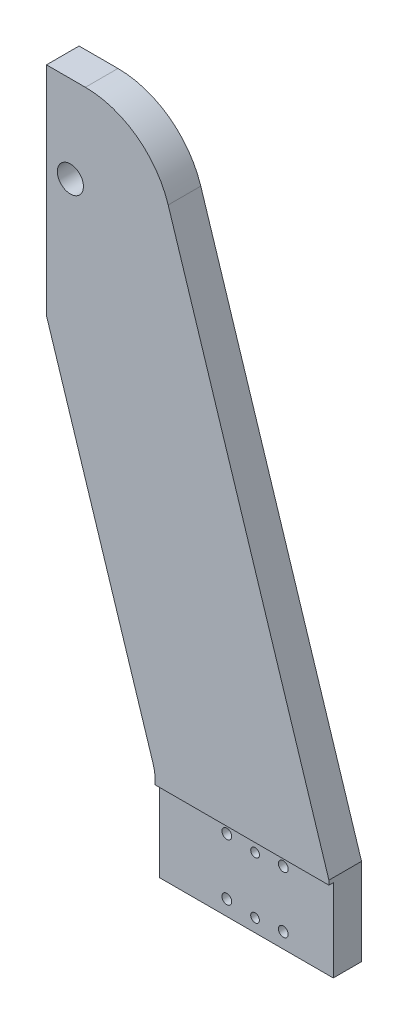
SolidWorks part; units mm, degrees
ref_plane "Alzado" through (0, 0, 0) normal (0, 0, 1) x (1, 0, 0)
ref_plane "Planta" through (0, 0, 0) normal (0, 1, 0) x (1, 0, 0)
ref_plane "Vista lateral" through (0, 0, 0) normal (1, 0, 0) x (0, 0, -1)
sketch "Croquis1" plane through (0, 0, 0) normal (0, 0, 1) x (1, 0, 0)
  line L0 (80, 0) -> (80, 40)
  line L1 (-50, 300) -> (-32.095, 300)
  line L2 (-50, 300) -> (-50, 200)
  line L3 (0, 0) -> (80, 0)
  line L4 (6.0164, 272.1459) -> (80, 40)
  line L9 (-50, 200) -> (-0.9443, 46.0729)
  line L11 (0, 40) -> (0, 0)
  arc A2 (6.0164, 272.1459) -> (-32.095, 300) centre (-32.095, 260) ccw
  arc A3 (-0.9443, 46.0729) -> (0, 40) centre (-20, 40) cw
  dimension "D7" = 40
  dimension "D9" = 40
  dimension "D4" = 20
  dimension "D1" = 50
  dimension "D2" = 300
  dimension "D3" = 80
  dimension "D5" = 100
  dimension "D6" = 40
extrude "Saliente-Extruir1" add sketch "Croquis1" along normal blind 15
sketch "Croquis2" plane through (0, 0, 0) normal (0, 0, -1) x (-1, 0, 0)
  line L0 (32.095, 300) -> (50, 300) construction
  line L2 (50, 300) -> (50, 200) construction
  circle A0 centre (39, 260) radius 6
  dimension "D3" = 12
  dimension "D1" = 40
  dimension "D2" = 11
extrude "Cortar-Extruir1" cut sketch "Croquis2" against normal through all
hole_wizard "Perforador para roscar para macho de roscar para M44" positions "Croquis7" profile "Croquis8" hole size "M4" standard "DIN"
sketch "Croquis7" plane through (0, 0, 0) normal (0, 0, -1) x (-1, 0, 0)
  line L0 (39, 278.25) -> (39, 241.75)
  circle A0 centre (39, 260) radius 6 construction
  point P10 (39, 278.25)
  point P12 (39, 241.75)
  dimension "D1" = 18.25
  dimension "D2" = 18.25
sketch "Croquis8" plane through (-39, 241.75, 0) normal (1, 0, 0) x (0, 1, 0)
  line L0 (0, 0) -> (0, 7.9914)
  line L1 (0, 7.9914) -> (1.65, 7)
  line L2 (1.65, 7) -> (1.65, 0)
  line L5 (1.65, 0) -> (0, 0)
  line L10 (0, 7.9914) -> (-1.65, 7) construction
  line L11 (0, -6.35) -> (0, 107.95) construction
  dimension "Diámetro de taladro" = 3.3
  dimension "Profundidad de taladro" = 7
  dimension "Ángulo de perforador" = 118
sketch "Croquis9" plane through (0, 0, 15) normal (0, 0, 1) x (1, 0, 0)
  line L1 (0, 0) -> (80, 0)
  line L2 (0, 0) -> (0, 38)
  line L3 (0, 38) -> (80, 38)
  line L4 (80, 0) -> (80, 38)
  dimension "D1" = 80
  dimension "D2" = 38
extrude "Cortar-Extruir2" cut sketch "Croquis9" against normal blind 2
hole_wizard "Taladros de espiga de Ø4.0mm1" positions "Croquis10" profile "Croquis12" hole size "Ø4.0" standard "DIN"
sketch "Croquis10" plane through (-50, 0, 0) normal (-1, 0, 0) x (0, 0, 1)
  line L0 (0, 300) -> (0, 200) construction
  line L1 (15, 300) -> (0, 300) construction
  point P0 (6, 274)
  point P2 (6, 246)
  dimension "D1" = 6
  dimension "D2" = 6
  dimension "D3" = 26
  dimension "D4" = 54
sketch "Croquis12" plane through (-50, 274, 6) normal (0, 1, 0) x (0, 0, 1)
  line L0 (0, 0) -> (0, 18.2017)
  line L1 (0, 18.2017) -> (2, 17)
  line L2 (2, 17) -> (2, 0)
  line L5 (2, 0) -> (0, 0)
  line L10 (0, 18.2017) -> (-2, 17) construction
  line L11 (0, -6.35) -> (0, 107.95) construction
  dimension "Diámetro de taladro" = 4
  dimension "Profundidad de taladro" = 17
  dimension "Ángulo de perforador" = 118
hole_wizard "Taladro roscado M41" positions "Croquis13" profile "Croquis14" tap size "M4" standard "DIN"
sketch "Croquis13" plane through (-50, 0, 0) normal (-1, 0, 0) x (0, 0, 1)
  line L0 (0, 300) -> (0, 200) construction
  line L1 (15, 300) -> (0, 300) construction
  point P0 (6, 285)
  point P2 (6, 235)
  dimension "D1" = 6
  dimension "D2" = 6
  dimension "D3" = 15
  dimension "D4" = 65
sketch "Croquis14" plane through (-50, 285, 6) normal (0, 1, 0) x (0, 0, 1)
  line L0 (0, 0) -> (0, 12.4914)
  line L1 (0, 12.4914) -> (1.65, 11.5)
  line L2 (1.65, 11.5) -> (1.65, 0)
  line L5 (1.65, 0) -> (0, 0)
  line L10 (0, 12.4914) -> (-1.65, 11.5) construction
  line L11 (0, -6.35) -> (0, 107.95) construction
  dimension "Diámetro de perforador para roscar" = 3.3
  dimension "Profundidad de perforador para roscar" = 11.5
  dimension "Ángulo de perforador" = 118
cosmetic thread "Rosca de taladro1" parameters "D1"=8, "D2"=4
cosmetic thread "Rosca de taladro2" parameters "D1"=8, "D2"=4
hole_wizard "Refrentado para tornillo con cabeza hueca de M41" positions "Croquis15" profile "Croquis16" counterbore size "M4" standard "DIN" end condition through all
sketch "Croquis15" plane through (0, 0, 0) normal (0, 0, -1) x (-1, 0, 0)
  line L1 (-57, 7) -> (-31, 7)
  line L2 (-57, 7) -> (-57, 33)
  line L3 (-57, 33) -> (-31, 33)
  line L4 (-31, 7) -> (-31, 33)
  line L5 (-57, 7) -> (-31, 33) construction
  line L6 (-57, 33) -> (-31, 7) construction
  line L16 (0, 0) -> (-80, 0) construction
  line L17 (-80, 0) -> (-80, 40) construction
  point P148 (-57, 33)
  point P151 (-31, 33)
  point P154 (-31, 7)
  point P157 (-57, 7)
  dimension "D1" = 26
  dimension "D2" = 26
  dimension "D3" = 23
  dimension "D4" = 7
sketch "Croquis16" plane through (57, 7, 0) normal (1, 0, 0) x (0, 1, 0)
  line L0 (0, 0) -> (0, 15)
  line L1 (0, 15) -> (2.25, 15)
  line L3 (2.25, 15) -> (2.25, 4.4)
  line L4 (2.25, 4.4) -> (4, 4.4)
  line L5 (4, 4.4) -> (4, 0)
  line L7 (4, 0) -> (0, 0)
  line L11 (0, -6.35) -> (0, 107.95) construction
  dimension "Diámetro de taladro hasta el siguiente" = 4.5
  dimension "Profundidad de taladro hasta el siguiente" = 15
  dimension "Diámetro de refrentado" = 8
  dimension "Profundidad de refrentado" = 4.4
hole_wizard "Taladros de espiga de Ø4.0mm2" positions "Croquis17" profile "Croquis18" hole size "Ø4.0" standard "DIN" end condition through all
sketch "Croquis17" plane through (0, 0, 0) normal (0, 0, -1) x (-1, 0, 0)
  line L0 (-44, 32) -> (-44, 6) construction
  line L2 (0, 0) -> (-80, 0) construction
  line L3 (-80, 0) -> (-80, 40) construction
  point P0 (-44, 32)
  point P2 (-44, 6)
  dimension "D1" = 26
  dimension "D2" = 6
  dimension "D3" = 36
sketch "Croquis18" plane through (44, 32, 0) normal (1, 0, 0) x (0, 1, 0)
  line L0 (0, 0) -> (0, 15)
  line L1 (0, 15) -> (2, 15)
  line L2 (2, 15) -> (2, 0)
  line L5 (2, 0) -> (0, 0)
  line L11 (0, -6.35) -> (0, 107.95) construction
  dimension "Diámetro de taladro hasta el siguiente" = 4
  dimension "Profundidad de taladro hasta el siguiente" = 15
